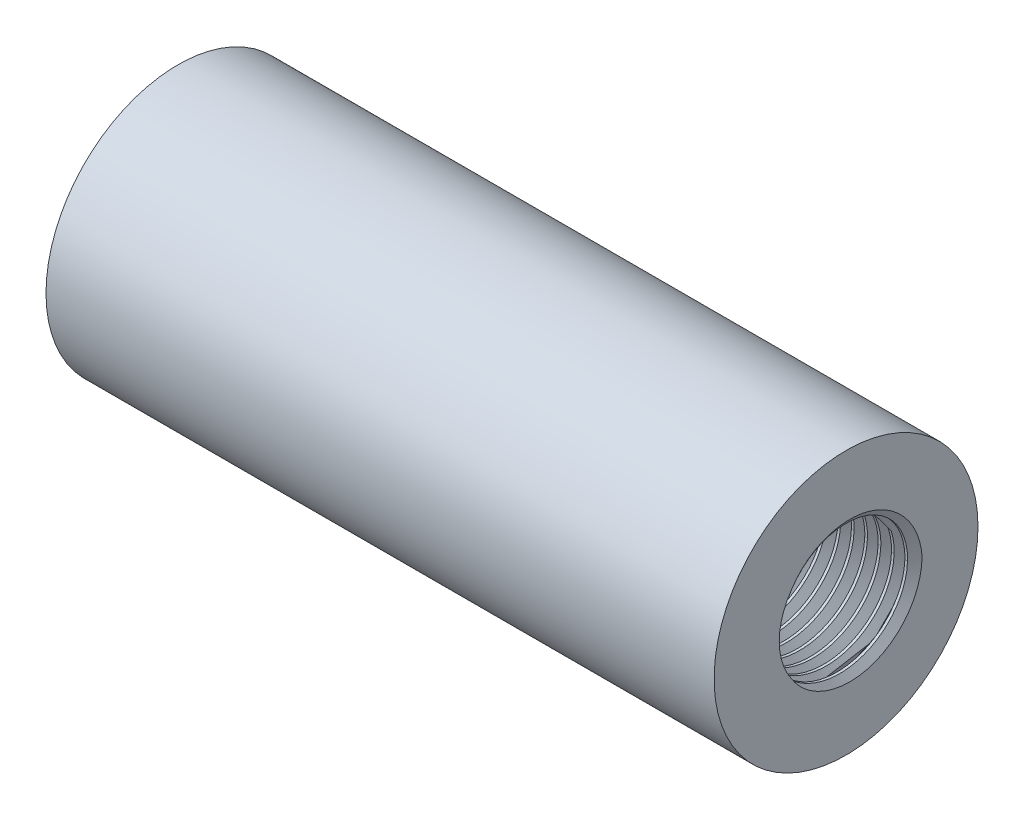
SolidWorks part; units mm, degrees
ref_plane "Front Plane" through (0, 0, 0) normal (0, 0, 1) x (1, 0, 0)
ref_plane "Top Plane" through (0, 0, 0) normal (0, 1, 0) x (1, 0, 0)
ref_plane "Right Plane" through (0, 0, 0) normal (1, 0, 0) x (0, 0, -1)
sketch "Sketch1" plane through (0, 0, 0) normal (1, 0, 0) x (0, 0, -1)
  circle A0 centre (0, 0) radius 7.9375
  dimension "D1" = 15.875
extrude "Boss-Extrude1" add sketch "Sketch1" against normal blind 332
sketch "Sketch2" plane through (0, 0, 0) normal (1, 0, 0) x (0, 0, -1)
  circle A0 centre (0, 0) radius 2.5
  dimension "D1" = 5
extrude "Cut-Extrude1" cut sketch "Sketch2" against normal blind 24
sketch "Sketch3" plane through (-332, 0, 0) normal (-1, 0, 0) x (0, 0, 1)
  circle A0 centre (0, 0) radius 2.5
  dimension "D1" = 5
extrude "Cut-Extrude2" cut sketch "Sketch3" against normal blind 24
sketch "Sketch4" plane through (0, 0, 0) normal (1, 0, 0) x (0, 0, -1)
  circle A0 centre (0, 0) radius 2.5
  dimension "D1" = 5
curve "Helix/Spiral1" pitch 0.5 height 18 radius 2.5 centre (0, 0, 0) axis (-1, 0, 0) start towards (0, 0, -1)
sketch "Sketch5" plane through (0, 0, 0) normal (1, 0, 0) x (0, 0, -1)
  line L1 (2.5, 0) -> (0, 0) construction
  circle A0 centre (0, 0) radius 2.5 construction
sketch3d "3DSketch5"
  point P0 (0, 0, -2.5)
sketch3d "3DSketch6"
  line L0 (0.2, 0, -2.5) -> (-0.2, 0, -2.5)
  line L2 (0.2, 0, -2.5) -> (-0.0014, 0, -2.8472)
  line L3 (-0.0014, 0, -2.8472) -> (-0.2, 0, -2.5)
  point P11 (0, 0, -2.5)
  dimension "D1" = 0.4
  dimension "D2" = 0.4
sweep "Cut-Sweep5" cut profiles "3DSketch6" path "Helix/Spiral1" align with end faces yes
sketch "Sketch8" plane through (-332, 0, 0) normal (-1, 0, 0) x (0, 0, 1)
  circle A0 centre (0, 0) radius 2.5
chamfer "Chamfer1" distance 3 angle 45 2 edges at (-332, 0, -7.9375) (0, 0, -7.9375)
sketch "Sketch10" plane through (0, 0, 0) normal (1, 0, 0) x (0, 0, -1)
  circle A0 centre (0, 0) radius 4.9375
extrude "Cut-Extrude3" cut sketch "Sketch10" against normal through all flip side to cut
sketch "Sketch13" plane through (0, 0, 0) normal (1, 0, 0) x (0, 0, -1)
  line L1 (5.3119, 5.2693) -> (-5.5567, 5.2693)
  line L2 (5.3119, 5.2693) -> (5.3119, -5.5093)
  line L3 (5.3119, -5.5093) -> (-5.5567, -5.5093)
  line L4 (-5.5567, 5.2693) -> (-5.5567, -5.5093)
extrude "Cut-Extrude4" cut sketch "Sketch13" against normal through all from offset 25 offset against normal yes
